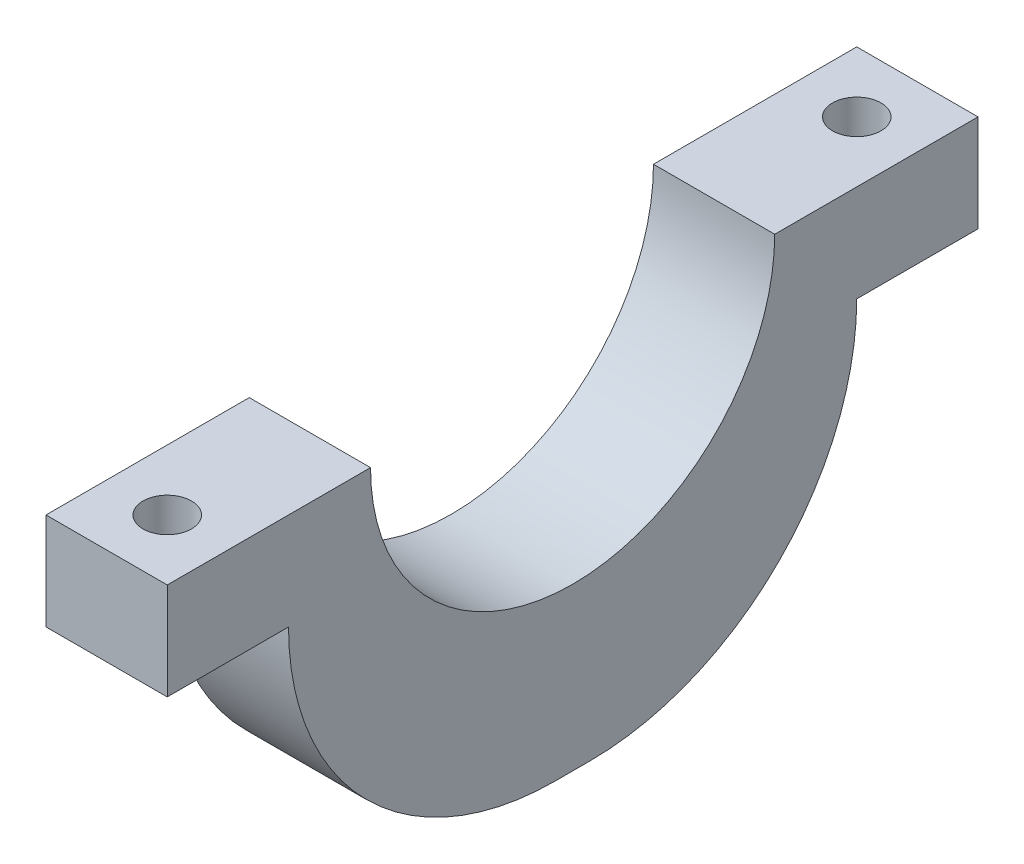
SolidWorks part; units mm, degrees
material "ABS"
ref_plane "Front Plane" through (0, 0, 0) normal (0, 0, 1) x (1, 0, 0)
ref_plane "Top Plane" through (0, 0, 0) normal (0, 1, 0) x (1, 0, 0)
ref_plane "Right Plane" through (0, 0, 0) normal (1, 0, 0) x (0, 0, -1)
sketch "Sketch1" plane through (0, 0, 0) normal (0, 1, 0) x (1, 0, 0)
  line L0 (-58.5, -56.5) -> (58.5, -56.5)
  line L1 (-58.5, -56.5) -> (-58.5, 56.5)
  line L2 (58.5, -56.5) -> (58.5, 56.5)
  line L3 (-58.5, 56.5) -> (58.5, 56.5)
  line L4 (-58.5, -56.5) -> (58.5, 56.5) construction
  line L5 (58.5, -56.5) -> (-58.5, 56.5) construction
  line L6 (-63.5, -61.5) -> (-63.5, 61.5)
  line L7 (-63.5, 61.5) -> (63.5, 61.5)
  line L8 (63.5, -61.5) -> (63.5, 61.5)
  line L9 (-63.5, -61.5) -> (63.5, -61.5)
  point P1 (0, 0)
  dimension "D1" = 117
  dimension "D2" = 113
  dimension "D3" = 5
extrude "Boss-Extrude1" add sketch "Sketch1" along normal blind 15
fillet "Fillet1" radius 10 1 edges at (58.5, 7.5, -56.5)
fillet "Fillet2" radius 10 1 edges at (-58.5, 7.5, -56.5)
fillet "Fillet3" radius 10 1 edges at (-58.5, 7.5, 56.5)
fillet "Fillet4" radius 10 1 edges at (58.5, 7.5, 56.5)
sketch "Sketch4" plane through (0, 15, 0) normal (0, 1, 0) x (1, 0, 0)
  line L0 (-63.5, 61.5) -> (-63.5, 63.125)
  line L1 (-63.5, 63.125) -> (-62.175, 63.125)
  line L2 (-62.175, 63.125) -> (-62.175, 80.6975)
  line L3 (-62.175, 80.6975) -> (-58.425, 80.6975)
  line L4 (-65.925, 45.5525) -> (-65.925, 80.6975)
  line L5 (-65.925, 45.5525) -> (-58.425, 45.5525)
  line L6 (-65.925, 80.6975) -> (-58.425, 80.6975)
  line L7 (-58.425, 45.5525) -> (-58.425, 80.6975)
  line L8 (-65.925, 45.5525) -> (-58.425, 80.6975) construction
  line L9 (-65.925, 80.6975) -> (-58.425, 45.5525) construction
  dimension "D1" = 1.625
  dimension "D2" = 1.325
  dimension "D3" = 3.75
extrude "Boss-Extrude3" add sketch "Sketch4" along normal blind 49.75 and the other way up to surface contours L6 L4 L5 L7
sketch "Sketch5" plane through (-58.425, 0, 0) normal (1, 0, 0) x (0, 0, -1)
  line L0 (45.5525, 64.75) -> (80.6975, 64.75) construction
  circle A0 centre (63.125, 64.75) radius 12.5
  dimension "D1" = 25
extrude "Cut-Extrude1" cut sketch "Sketch5" against normal through all
ref_plane "Plane1" through (-62.175, 0, 0) normal (1, 0, 0) x (0, 0, -1)
sketch "Sketch6" plane through (-58.425, 0, 0) normal (1, 0, 0) x (0, 0, -1)
  line L0 (45.5525, 64.75) -> (50.625, 64.75)
  line L1 (45.5525, 64.75) -> (45.5525, 57.25)
  line L2 (45.5525, 0) -> (45.5525, 64.75) construction
  line L3 (45.5525, 57.25) -> (53.125, 57.25)
  arc A0 (50.625, 64.75) -> (75.625, 64.75) centre (63.125, 64.75) ccw construction
  arc A1 (53.125, 57.25) -> (50.625, 64.75) centre (63.125, 64.75) cw
  dimension "D1" = 7.5
extrude "Boss-Extrude4" add sketch "Sketch6" along normal blind 5
sketch "Sketch9" plane through (0, 64.75, 0) normal (0, 1, 0) x (1, 0, 0)
  line L0 (-53.425, 48.0887) -> (-55.925, 48.0887)
  line L1 (-53.425, 50.625) -> (-53.425, 45.5525) construction
  circle A0 centre (-55.925, 48.0887) radius 1.25
  dimension "D2" = 2.5
  dimension "D1" = 2.5
extrude "Cut-Extrude3" cut sketch "Sketch9" against normal through all
mirror "Mirror1" about plane through (-62.175, 0, 0) normal (1, 0, 0) of "Cut-Extrude3", "Boss-Extrude4"
ref_plane "Plane2" through (0, 0, -63.125) normal (0, 0, -1) x (-1, 0, 0)
mirror "Mirror2" about plane through (0, 0, -63.125) normal (0, 0, -1) of "Mirror1", "Boss-Extrude4", "Cut-Extrude3"
fillet "Fillet6" radius 17.5 1 edges at (-58.425, 7.5, -61.5)
fillet "Fillet7" radius 17.5 3 edges at (-53.2994, 15, -66.6256) (-55.1248, 15, -53.9908) (-58.425, 15, -63.3612)
fillet "Fillet8" radius 2 1 edges at (-63.5, 7.5, -45.5525)
fillet "Fillet9" radius 17.5 2 edges at (-64.0858, 15, -44.9667) (-62, 15, -45.5525)
fillet "Fillet10" radius 17.5 2 edges at (-58.425, 0, -79.8488) (-62.175, 0, -80.6975)
mirror "Mirror4" about plane through (0, 0, 0) normal (0, 0, 1) of "Mirror2", "Mirror1", "Cut-Extrude3", "Boss-Extrude4", "Cut-Extrude1", "Boss-Extrude3"
fillet "Fillet11" radius 2 1 edges at (-63.5, 7.5, 45.5525)
fillet "Fillet12" radius 17.5 2 edges at (-62, 15, 45.5525) (-64.0858, 15, 44.9667)
fillet "Fillet13" radius 17.5 1 edges at (-58.425, 7.5, 61.5)
fillet "Fillet14" radius 17.5 3 edges at (-55.1248, 15, 53.9908) (-58.425, 15, 63.3612) (-53.2994, 15, 66.6256)
fillet "Fillet15" radius 17.5 2 edges at (-58.425, 0, 79.8488) (-62.175, 0, 80.6975)
mirror "Mirror6" about plane through (0, 0, 0) normal (1, 0, 0) of "Mirror4", "Boss-Extrude3", "Boss-Extrude4", "Cut-Extrude3", "Mirror1", "Mirror2"
fillet "Fillet16" radius 2 1 edges at (63.5, 7.5, 45.5525)
fillet "Fillet17" radius 17.5 2 edges at (62, 15, 45.5525) (64.0858, 15, 44.9667)
fillet "Fillet18" radius 2 1 edges at (63.5, 7.5, -45.5525)
fillet "Fillet19" radius 17.5 2 edges at (62, 15, -45.5525) (64.0858, 15, -44.9667)
fillet "Fillet20" radius 17.5 1 edges at (58.425, 7.5, -61.5)
fillet "Fillet21" radius 17.5 3 edges at (55.1248, 15, -53.9908) (58.425, 15, -63.3612) (53.2994, 15, -66.6256)
fillet "Fillet22" radius 17.5 1 edges at (58.425, 7.5, 61.5)
fillet "Fillet23" radius 17.5 3 edges at (58.425, 15, 63.3612) (55.1248, 15, 53.9908) (53.2994, 15, 66.6256)
fillet "Fillet24" radius 17.5 2 edges at (58.425, 0, 79.8488) (62.175, 0, 80.6975)
fillet "Fillet25" radius 17.5 2 edges at (58.425, 0, -79.8488) (62.175, 0, -80.6975)
sketch "Sketch11" plane through (0, 0, 0) normal (0, -1, 0) x (-1, 0, 0)
  line L0 (0, 0) -> (0, 45.4)
  line L1 (0, 45.4) -> (-47.5, 45.4)
  line L3 (-35.6125, 0) -> (35.6125, 0) construction
  line L4 (0, 35.6125) -> (0, -35.6125) construction
  line L5 (-47.5, 45.4) -> (47.5, -45.4)
  line L6 (47.5, -45.4) -> (41.3679, -51.8158)
  line L7 (41.3679, -51.8158) -> (-58.5, 43.6368)
  line L8 (-58.5, -45.5525) -> (-58.5, 45.5525) construction
  line L9 (41.3679, -51.8158) -> (45.5521, -56.5)
  line L10 (48.5, -56.5) -> (-48.5, -56.5) construction
  line L11 (47.5, -45.4) -> (53.7617, -39.1106)
  line L12 (-47.5, 45.4) -> (-41.2244, 51.6756)
  line L13 (-41.2244, 51.6756) -> (53.7617, -39.1106)
  line L14 (53.7617, -39.1106) -> (58.5, -43.6395)
  line L15 (58.5, 45.5525) -> (58.5, -45.5525) construction
  line L16 (-41.2244, 51.6756) -> (-46.272, 56.5)
  line L17 (-48.5, 56.5) -> (48.5, 56.5) construction
  circle A0 centre (-47.5, 45.4) radius 6
  circle A1 centre (-47.5, 45.4) radius 8.875
  circle A4 centre (-47.5, -45.4) radius 8.875
  circle A5 centre (-47.5, -45.4) radius 6
  circle A6 centre (47.5, 45.4) radius 8.875
  circle A7 centre (47.5, 45.4) radius 6
  circle A8 centre (47.5, -45.4) radius 8.875
  circle A9 centre (47.5, -45.4) radius 6
  arc A10 (-58.5, 43.6368) -> (-46.272, 56.5) centre (-48.0688, 45.9644) cw
  arc A11 (45.5521, -56.5) -> (58.5, -43.6395) centre (49.0059, -47.0291) ccw
  line M27 (-58.5, -45.5525) -> (-58.5, 45.5525)
  line M28 (-58.5, 45.5525) -> (-58.425, 45.5525)
  line M29 (-58.425, 45.5525) -> (-58.425, 47.7224)
  arc M30 (-58.425, 47.7224) -> (-48.5, 56.5) centre (-48.5, 46.5) cw
  line M31 (-48.5, 56.5) -> (48.5, 56.5)
  line M35 (58.5, 45.5525) -> (58.5, -45.5525)
  line M36 (58.5, -45.5525) -> (58.425, -45.5525)
  line M37 (58.425, -45.5525) -> (58.425, -47.7224)
  arc M38 (58.425, -47.7224) -> (48.5, -56.5) centre (48.5, -46.5) cw
  line M39 (48.5, -56.5) -> (-48.5, -56.5)
  dimension "D3" = 12
  dimension "D4" = 17.75
  dimension "D1" = 45.4
  dimension "D2" = 47.5
extrude "Boss-Extrude5" add sketch "Sketch11" against normal blind 3.5 contours A8 L9 L14 M39 M38 M37 M36 M35 | A9 L6 A8 L11 | A9 L5 A8 L6 | A9 L11 L13 A8 L5 | A8 L5 A1 L7 | A8 L13 L0 L5 | A1 L5 L0 L13 L1 | A1 L1 L13 | L5 A1 L1 A0 | L1 A1 L12 A0 | A1 L5 A0 L12 L16 | A1 L16 L7 M31 M30 M29 M28 M27
mirror "Mirror7" about plane through (0, 0, 0) normal (0, 0, 1) of "Boss-Extrude5"
sketch "Sketch12" plane through (0, 0, 0) normal (0, -1, 0) x (-1, 0, 0)
  line L0 (0, 0) -> (-4, 0)
  line L1 (0, 0) -> (-0.36, 56.5)
  line L2 (-46.272, 56.5) -> (45.5521, 56.5) construction
  line L3 (4, -56.5079) -> (-4, -56.5079)
  line L4 (4, -56.5079) -> (4, 56.5079)
  line L5 (-4, -56.5079) -> (-4, 56.5079)
  line L6 (4, 56.5079) -> (-4, 56.5079)
  line L7 (4, -56.5079) -> (-4, 56.5079) construction
  line L8 (-4, -56.5079) -> (4, 56.5079) construction
  line M6 (-46.272, -56.5) -> (-0.0015, -12.2754)
  line M7 (-0.0015, -12.2754) -> (41.3679, -51.8158)
  line M9 (45.5521, -56.5) -> (-46.272, -56.5)
  line M13 (41.3679, 51.8158) -> (-0.0015, 12.2754)
  line M14 (-0.0015, 12.2754) -> (-46.272, 56.5)
  line M15 (-46.272, 56.5) -> (45.5521, 56.5)
  dimension "D1" = 4
extrude "Boss-Extrude6" add sketch "Sketch12" against normal up to surface (3.5 mm away) contours L4 L1 M13 M15 M14 | L5 L1 M14 M15 | L5 L4 M9 M7 M6 up to face at (47.5, 3.5, -51.4)
sketch "Sketch13" plane through (0, 0, 0) normal (0, -1, 0) x (-1, 0, 0)
  line L0 (0, 0) -> (0, 42.5)
  circle A0 centre (0, 42.5) radius 1.5
  dimension "D2" = 3
  dimension "D1" = 42.5
extrude "Cut-Extrude4" cut sketch "Sketch13" against normal through all
mirror "Mirror8" about plane through (0, 0, 0) normal (0, 0, 1) of "Cut-Extrude4"
sketch "Sketch14" plane through (0, 57.25, 0) normal (0, -1, 0) x (-1, 0, 0)
  line L1 (65.925, -73.125) -> (70.925, -73.125)
  line L2 (65.925, -73.125) -> (65.925, -80.6975)
  line L3 (65.925, -80.6975) -> (70.925, -80.6975)
  line L4 (70.925, -73.125) -> (70.925, -80.6975)
  line L5 (53.425, -73.125) -> (58.425, -73.125)
  line L6 (53.425, -73.125) -> (53.425, -80.6975)
  line L7 (53.425, -80.6975) -> (58.425, -80.6975)
  line L8 (58.425, -73.125) -> (58.425, -80.6975)
  line L9 (65.925, -53.125) -> (70.925, -53.125)
  line L10 (65.925, -53.125) -> (65.925, -45.5525)
  line L11 (65.925, -45.5525) -> (70.925, -45.5525)
  line L12 (70.925, -53.125) -> (70.925, -45.5525)
  line L13 (58.425, -53.125) -> (53.425, -53.125)
  line L14 (58.425, -53.125) -> (58.425, -45.5525)
  line L15 (58.425, -45.5525) -> (53.425, -45.5525)
  line L16 (53.425, -53.125) -> (53.425, -45.5525)
extrude "Cut-Extrude5" cut sketch "Sketch14" against normal through all
mirror "Mirror9" about plane through (0, 0, 0) normal (0, 0, 1) of "Cut-Extrude5"
mirror "Mirror10" about plane through (0, 0, 0) normal (1, 0, 0) of "Mirror9", "Cut-Extrude5"
sketch "Sketch15" plane through (0, 64.75, 0) normal (0, 1, 0) x (1, 0, 0)
  line L0 (-65.925, -80.6975) -> (-65.925, -88.1975)
  line L2 (-65.925, -88.1975) -> (-58.425, -88.1975)
  line L3 (-65.925, -88.1975) -> (-65.925, -80.6975)
  line L4 (-65.925, -80.6975) -> (-58.425, -80.6975)
  line L5 (-58.425, -88.1975) -> (-58.425, -80.6975)
  line M2 (-65.925, -80.6975) -> (-58.425, -80.6975)
  dimension "D1" = 7.5
extrude "Boss-Extrude7" add sketch "Sketch15" against normal blind 6 contours L2 L5 L0 M2
sketch "Sketch16" plane through (0, 58.75, 0) normal (0, -1, 0) x (-1, 0, 0)
  line L0 (58.425, -84.4475) -> (65.925, -84.4475)
  line L1 (58.425, -88.1975) -> (58.425, -80.6975) construction
  line L2 (65.925, -80.6975) -> (65.925, -88.1975) construction
  circle A0 centre (62.175, -84.4475) radius 1.5
  dimension "D1" = 3
extrude "Cut-Extrude6" cut sketch "Sketch16" against normal through all contours A0
ref_plane "Plane3" through (0, 0, 63.125) normal (0, 0, 1) x (1, 0, 0)
mirror "Mirror11" about plane through (0, 0, 63.125) normal (0, 0, 1) of "Cut-Extrude6", "Boss-Extrude7"
mirror "Mirror12" about plane through (0, 0, 0) normal (0, 0, 1) of "Mirror11", "Cut-Extrude6", "Boss-Extrude7"
mirror "Mirror13" about plane through (0, 0, 0) normal (1, 0, 0) of "Mirror12", "Mirror11", "Cut-Extrude6", "Boss-Extrude7"
ref_plane "Plane4" through (0, 42.25, 0) normal (0, 1, 0) x (1, 0, 0)
sketch "Sketch17" plane through (0, 42.25, 0) normal (0, 1, 0) x (1, 0, 0)
  circle A0 centre (0, 0) radius 238.6374
extrude "Cut-Extrude7" cut sketch "Sketch17" against normal through all
sketch "Sketch18" plane through (0, 0, 0) normal (0, 0, 1) x (1, 0, 0)
  circle A0 centre (0, 0) radius 360.9972
extrude "Cut-Extrude8" cut sketch "Sketch18" against normal through all
sketch "Sketch20" plane through (0, 0, 0) normal (1, 0, 0) x (0, 0, -1)
  circle A0 centre (0, 0) radius 427.0854
extrude "Cut-Extrude10" cut sketch "Sketch20" along normal through all
fillet "Fillet26" radius 16.5 3 edges at (-65.925, 50.5, 80.6975) (-58.425, 50.5, 80.6975) (-62.175, 42.25, 80.6975)
fillet "Fillet27" radius 16.5 3 edges at (-58.425, 50.5, 45.5525) (-62.175, 42.25, 45.5525) (-65.925, 50.5, 45.5525)
sketch "Sketch21" plane through (0, 0, 63.125) normal (0, 0, 1) x (1, 0, 0)
  circle A0 centre (0, 0) radius 144.0686
